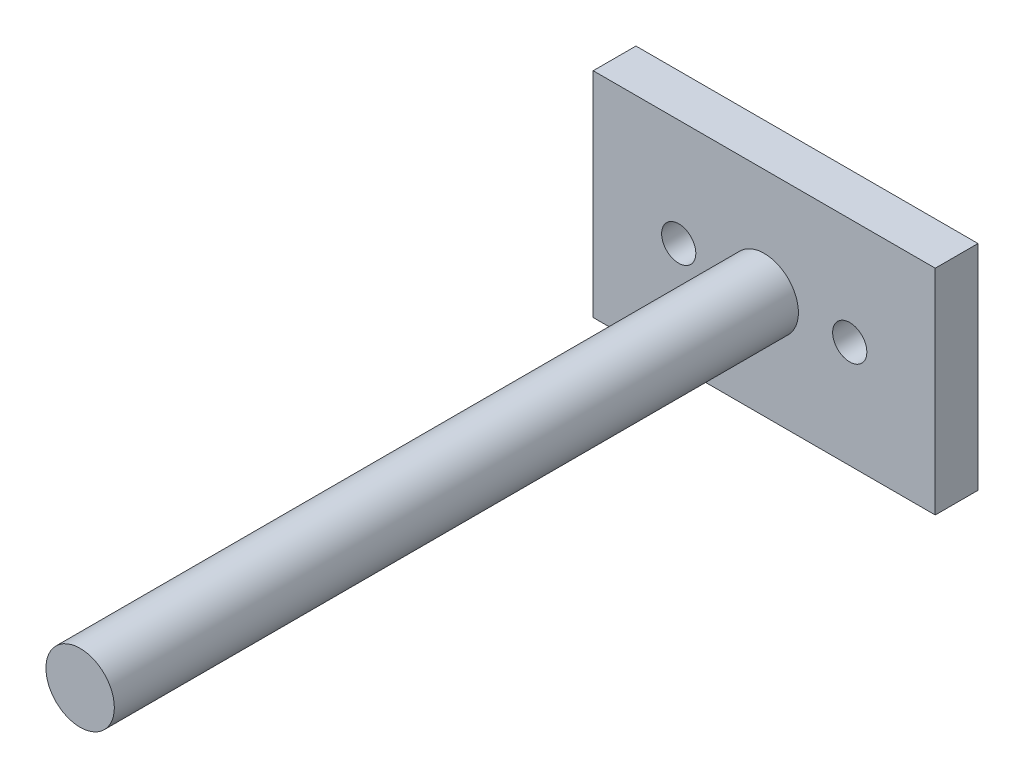
SolidWorks part; units mm, degrees
ref_plane "Plano frontal" through (0, 0, 0) normal (0, 0, 1) x (1, 0, 0)
ref_plane "Plano superior" through (0, 0, 0) normal (0, 1, 0) x (1, 0, 0)
ref_plane "Plano direito" through (0, 0, 0) normal (1, 0, 0) x (0, 0, -1)
sketch "Esboço1" plane through (0, 0, 0) normal (0, 0, 1) x (1, 0, 0)
  line L1 (-20, -12.5) -> (20, -12.5)
  line L2 (-20, -12.5) -> (-20, 12.5)
  line L3 (-20, 12.5) -> (20, 12.5)
  line L4 (20, -12.5) -> (20, 12.5)
  line L5 (0, 12.5) -> (0, -12.5) construction
  line L6 (-20, 0) -> (20, 0) construction
  circle A0 centre (0, 0) radius 4
  circle A1 centre (10, 0) radius 2
  circle A2 centre (-10, 0) radius 2
extrude "Ressalto-extrusão1" add sketch "Esboço1" along normal blind 80 contours A0 region at (0, 0, 0)
extrude "Ressalto-extrusão2" add sketch "Esboço1<3>" against normal blind 5 separate body contours A0 | L1 L4 L3 L2 A0 region at (-19.5283, 0, 0) region at (0, 0, 0)
sketch "Esboço1<3>" plane through (0, 0, 0) normal (0, 0, 1) x (1, 0, 0) same geometry as "Esboço1"
